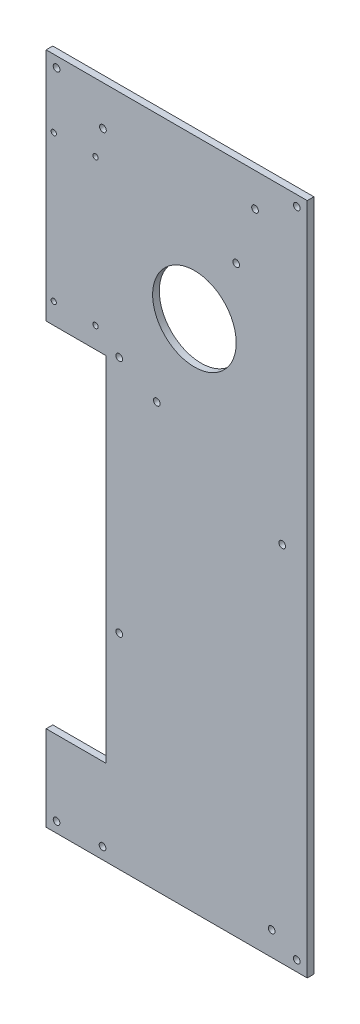
SolidWorks part; units mm, degrees
ref_plane "Front Plane" through (0, 0, 0) normal (1, 0, 0) x (0, 1, 0)
ref_plane "Top Plane" through (0, 0, 0) normal (0, 0, 1) x (0, 1, 0)
ref_plane "Right Plane" through (0, 0, 0) normal (0, 1, 0) x (-1, 0, 0)
sketch "Sketch1" plane through (0, 0, 0) normal (0, 0, 1) x (0, 1, 0)
  line L0 (-57.15, 6.35) -> (-57.15, 35)
  line L1 (-98, 6.35) -> (224.3, 6.35)
  line L2 (-98, 6.35) -> (-98, -90)
  line L3 (-98, -90) -> (224.3, -90)
  line L4 (224.3, 6.35) -> (224.3, -90)
  line L5 (-57.15, 35) -> (-98, 35)
  line L6 (-98, 35) -> (-98, 6.35)
  line L7 (196.85, 6.35) -> (196.85, 35)
  line L8 (196.85, 35) -> (224.3, 35)
  line L9 (224.3, 35) -> (224.3, 6.35)
  line L10 (196.85, 35) -> (111.85, 35)
  line L11 (121.85, 31.35) -> (191.85, 31.35) construction
  line L12 (121.85, 31.35) -> (121.85, 11.35) construction
  line L13 (121.85, 11.35) -> (191.85, 11.35) construction
  line L14 (191.85, 31.35) -> (191.85, 11.35) construction
  line L15 (111.85, 35) -> (111.85, 6.35)
  circle A0 centre (-86.5, -73) radius 1.6
  circle A1 centre (-92.5, 8) radius 1.6
  circle A2 centre (0, 0) radius 1.6
  circle A3 centre (114.3, 0) radius 1.6
  circle A4 centre (104.8, -18) radius 1.6
  circle A5 centre (181.3, -56) radius 1.6
  circle A6 centre (208.3, -65) radius 1.6
  circle A7 centre (205.3, 7.8) radius 1.6
  circle A8 centre (75.7, -78) radius 1.6
  circle A18 centre (148.3, -36) radius 20
  circle A19 centre (-93, 30) radius 1.6
  circle A20 centre (-93, -85) radius 1.6
  circle A21 centre (219.3, -85) radius 1.6
  circle A22 centre (219.3, 30) radius 1.6
  circle A23 centre (121.85, 31.35) radius 1.25
  circle A24 centre (121.85, 11.35) radius 1.25
  circle A25 centre (191.85, 11.35) radius 1.25
  circle A26 centre (191.85, 31.35) radius 1.25
  dimension "D1" = 3.2
  dimension "D13" = 78
  dimension "D23" = 3.2
  dimension "D26" = 34
  dimension "D27" = 40
  dimension "D29" = 5
  dimension "D34" = 2.5
  dimension "D2" = 114.3
  dimension "D3" = 8
  dimension "D4" = 92.5
  dimension "D5" = 73
  dimension "D6" = 86.5
  dimension "D7" = 98
  dimension "D8" = 110
  dimension "D9" = 91
  dimension "D10" = 7.8
  dimension "D11" = 94
  dimension "D12" = 65
  dimension "D14" = 38.6
  dimension "D15" = 9.5
  dimension "D16" = 18
  dimension "D17" = 67
  dimension "D18" = 56
  dimension "D19" = 90
  dimension "D20" = 6.35
  dimension "D21" = 57.15
  dimension "D22" = 35
  dimension "D24" = 5
  dimension "D25" = 82.55
  dimension "D28" = 36
  dimension "D30" = 5
  dimension "D31" = 5
  dimension "D32" = 20
  dimension "D33" = 70
  dimension "D35" = 5
  dimension "D36" = 5
  dimension "D37" = 10
extrude "Boss-Extrude1" add sketch "Sketch1" against normal blind 3.18 contours A7 L1 L2 L3 L4 A21 A20 A18 A8 A6 A5 A4 A3 A2 A0 | L5 L6 L1 L0 A19 A1 | A7 L1 L9 L8 L7 A22 | L10 L15 L1 L7 A26 A25 A24 A23 region at (-20.6983, -77.3635, 0) region at (42.0489, 59.5074, 0) region at (-20.6695, 154.3297, 0) region at (-20.7095, 210.5381, 0)
